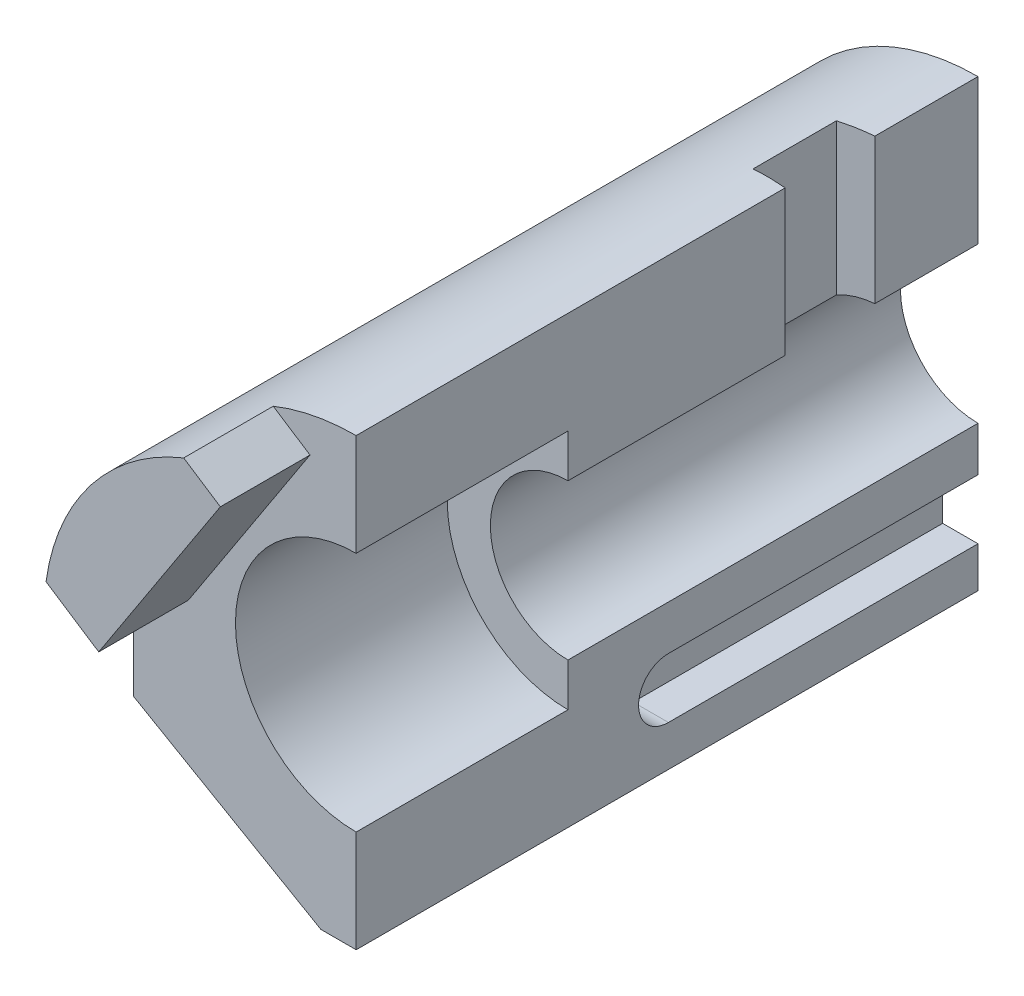
SolidWorks part; units mm, degrees
material "1060 Alloy"
ref_plane "Front Plane" through (0, 0, 0) normal (0, 0, 1) x (1, 0, 0)
ref_plane "Top Plane" through (0, 0, 0) normal (0, 1, 0) x (1, 0, 0)
ref_plane "Right Plane" through (0, 0, 0) normal (1, 0, 0) x (0, 0, -1)
sketch "Sketch2" plane through (0, 0, 0) normal (0, 0, 1) x (1, 0, 0)
  line L0 (0, 67.6091) -> (0, -76.2804) construction
  line L1 (0, 0) -> (-13, 0)
  line L2 (56.3635, 0) -> (-81.2935, 0) construction
  line L3 (-13, 0) -> (-82, 39.8372)
  line L4 (-82, 39.8372) -> (-82, 82)
  line L5 (0, 164) -> (0, 110.575)
  line L6 (0, 53.425) -> (0, 0)
  line L10 (-70.0722, 124.5897) -> (-70.0135, 124.6649)
  line L11 (-70.0135, 124.6649) -> (-70.0223, 124.6717) construction
  line L12 (0, 82) -> (-125.9546, 180.4065) construction
  line L13 (-82, 82) -> (0, 82) construction
  line L14 (-17.0064, 149.2921) -> (-61.7941, 80.604)
  line L15 (-17.0064, 149.2921) -> (-30.5248, 158.1067)
  line L16 (-61.7941, 80.604) -> (-81.2216, 93.2716)
  line L19 (-61.7941, 80.604) -> (-61.6202, 82) construction
  arc A0 (-82, 82) -> (0, 164) centre (0, 82) cw
  arc A2 (0, 110.575) -> (0, 53.425) centre (0, 82) ccw
  arc A3 (0, 126.45) -> (0, 37.55) centre (0, 82) ccw
  point P14 (0, 0)
  point P17 (-56.1535, 125.8719)
  point P19 (0, 0)
  point P26 (0, 0)
  point P28 (0, 0)
  point P30 (0, 0)
  point P31 (0, 0)
  point P32 (0, 0)
  point P33 (0, 0)
  point P34 (0, 0)
  point P35 (0, 0)
  point P36 (0, 0)
  point P37 (0, 0)
  point P38 (0, 0)
  point P39 (0, 0)
  point P40 (0, 0)
  point P41 (0, 0)
  point P42 (0, 0)
  point P43 (0, 0)
  point P44 (0, 0)
  dimension "D4" = 82
  dimension "D6" = 88.9
  dimension "D3" = 28.575
  dimension "D14" = 23.1925
  dimension "D11" = 164
  dimension "D1" = 30
  dimension "D2" = 82
  dimension "D5" = 13
  dimension "D7" = 82
  dimension "D9" = 53.425
  dimension "D10" = 51
  dimension "D12" = 82
  dimension "D13" = 16.1383
  dimension "D15" = 146.894
extrude "Boss-Extrude4" add sketch "Sketch2" against normal blind 229 contours A2 L6 L1 L3 L4 A0 L5
extrude "Cut-Extrude2" cut sketch "Sketch2<13>" against normal blind 78 contours L5 A3 L6 A2 region at (-43.4561, 82, 0)
sketch "Sketch2<13>" plane through (0, 0, 0) normal (0, 0, 1) x (1, 0, 0) same geometry as "Sketch2"
extrude "Boss-Extrude5" add sketch "Sketch2<14>" along normal blind 33 contours A0 L16 L14 L15 region at (-51.9174, 121.1187, 0)
sketch "Sketch2<14>" plane through (0, 0, 0) normal (0, 0, 1) x (1, 0, 0) same geometry as "Sketch2"
sketch "Sketch4" plane through (0, 0, 0) normal (1, 0, 0) x (0, 0, -1)
  line L0 (229, 26) -> (115, 26) construction
  line L1 (229, 53.425) -> (229, 0) construction
  line L2 (229, 15) -> (115, 15)
  line L3 (229, 37) -> (115, 37)
  arc A0 (229, 15) -> (229, 37) centre (229, 26) ccw
  arc A1 (115, 37) -> (115, 15) centre (115, 26) ccw
  point P4 (172, 26)
  dimension "D2" = 11
  dimension "D1" = 26
  dimension "D3" = 114
extrude "Cut-Extrude3" cut sketch "Sketch4" against normal blind 13
sketch "Sketch5" plane through (0, 0, 0) normal (1, 0, 0) x (0, 0, -1)
  line L6 (158, 183.4718) -> (191, 183.4718)
  line L7 (158, 183.4718) -> (158, 103.4718)
  line L8 (158, 103.4718) -> (191, 103.4718)
  line L9 (191, 183.4718) -> (191, 103.4718)
  dimension "D1" = 33
  dimension "D2" = 38
  dimension "D3" = 80
extrude "Cut-Extrude6" cut sketch "Sketch5" against normal blind 13 draft 5
